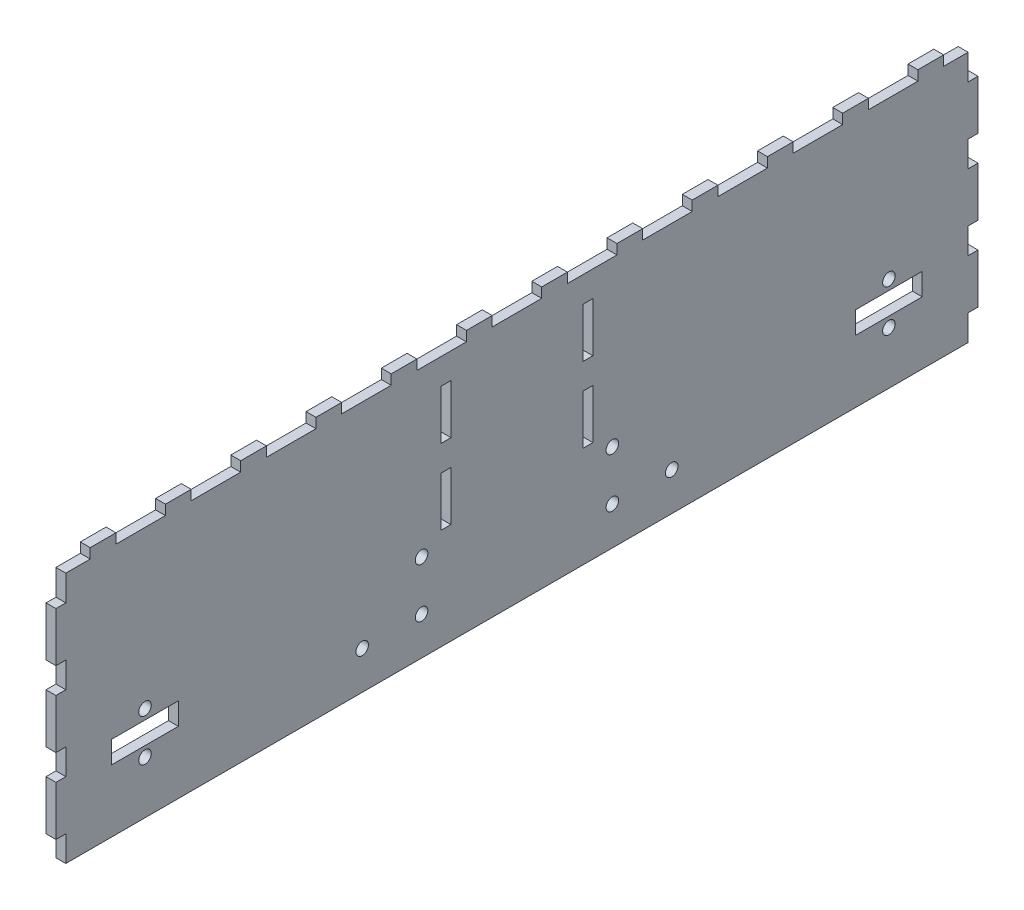
SolidWorks part; units mm, degrees
material "ENPH 253 Hardboard"
ref_plane "Front Plane" through (0, 0, 0) normal (0, 0, 1) x (1, 0, 0)
ref_plane "Top Plane" through (0, 0, 0) normal (0, 1, 0) x (1, 0, 0)
ref_plane "Right Plane" through (0, 0, 0) normal (1, 0, 0) x (0, 0, -1)
sketch "Sketch1" plane through (0, 0, 0) normal (1, 0, 0) x (0, 0, -1)
  line L1 (-139.7, 38.1) -> (139.7, 38.1)
  line L2 (-139.7, 38.1) -> (-139.7, -38.1)
  line L3 (-139.7, -38.1) -> (139.7, -38.1)
  line L4 (139.7, 38.1) -> (139.7, -38.1)
  line L5 (-139.7, 38.1) -> (139.7, -38.1) construction
  line L6 (-139.7, -38.1) -> (139.7, 38.1) construction
  point P0 (0, 0)
  dimension "D1" = 279.4
  dimension "D2" = 76.2
extrude "Boss-Extrude1" add sketch "Sketch1" against normal blind 3 contours L2 L3 L4 L1
sketch "Sketch3" plane through (-3, 0, 0) normal (-1, 0, 0) x (0, 0, 1)
  line L9 (-139.7, 38.1) -> (-136.7, 38.1)
  line L10 (-139.7, 38.1) -> (-139.7, 30.3)
  line L11 (-139.7, 30.3) -> (-136.7, 30.3)
  line L12 (-136.7, 38.1) -> (-136.7, 30.3)
  dimension "D9" = 7.8
  dimension "D10" = 3
extrude "Cut-Extrude1" cut sketch "Sketch3" against normal through all
pattern_linear "LPattern1" count 4 spacing 22.8 along (0, -1, 0) of "Cut-Extrude1"
mirror "Mirror1" about plane through (0, 0, 0) normal (0, 0, 1) of "LPattern1"
sketch "Sketch5" plane through (-3, 0, 0) normal (-1, 0, 0) x (0, 0, 1)
  line L1 (-23, 30.3) -> (-20, 30.3)
  line L2 (-23, 30.3) -> (-23, 15.3)
  line L3 (-23, 15.3) -> (-20, 15.3)
  line L4 (-20, 30.3) -> (-20, 15.3)
  line L5 (136.7, 38.1) -> (-136.7, 38.1) construction
  line L6 (0, -1.65) -> (0, 1.65) construction
  dimension "D1" = 20
  dimension "D2" = 3
  dimension "D3" = 7.8
  dimension "D4" = 15
extrude "Cut-Extrude3" cut sketch "Sketch5" against normal blind 10
sketch "Sketch9" plane through (0, 38.1, 0) normal (0, 1, 0) x (1, 0, 0)
  line L0 (0, -136.7) -> (0, 136.7) construction
  line L1 (0, 129.3) -> (-3, 129.3)
  line L2 (0, 129.3) -> (0, 121.5)
  line L3 (0, 121.5) -> (-3, 121.5)
  line L4 (-3, 129.3) -> (-3, 121.5)
  line L5 (-3, -136.7) -> (-3, 136.7) construction
  line L6 (0, 136.7) -> (-3, 136.7) construction
  point P10 (-1.5, 129.3)
  dimension "D1" = 7.4
  dimension "D2" = 7.8
extrude "Boss-Extrude2" add sketch "Sketch9" along normal blind 3
pattern_linear "LPattern4" count 12 spacing 22.8 along (0, 0, 1) of "Boss-Extrude2"
pattern_linear "LPattern5" count 2 spacing 22.8 along (0, -1, 0) of "Cut-Extrude3"
mirror "Mirror2" about plane through (0, 0, 0) normal (0, 0, 1) of "LPattern5"
hole_wizard "#6 Clearance Hole1" positions "Sketch10" profile "Sketch11" hole size "#6" standard "ANSI Inch" end condition up to next
sketch "Sketch10" plane through (0, 0, 0) normal (1, 0, 0) x (0, 0, -1)
  point P0 (-28.9, -11.55)
  point P3 (-28.9, -26.55)
  point P6 (28.9, -26.55)
  point P9 (28.9, -11.55)
  point P13 (-46.9, -26.55)
  point P16 (46.9, -26.55)
sketch "Sketch11" plane through (0, -11.55, 28.9) normal (0, 1, 0) x (0, 0, -1)
  line L0 (0, 0) -> (0, 3)
  line L1 (0, 3) -> (1.8986, 3)
  line L2 (1.8986, 3) -> (1.8986, 0)
  line L5 (1.8986, 0) -> (0, 0)
  line L11 (0, -6.35) -> (0, 107.95) construction
  dimension "Thru Hole Dia." = 3.7973
  dimension "Thru Hole Depth" = 3
sketch "Sketch12" plane through (0, 0, 0) normal (1, 0, 0) x (0, 0, -1)
  line L0 (0, 38.1) -> (0, -38.1) construction
  line L1 (-122.7, -12.55) -> (-102.7, -12.55) construction
  line L2 (-122.7, -12.55) -> (-122.7, -19.05) construction
  line L3 (-122.7, -19.05) -> (-102.7, -19.05) construction
  line L4 (-102.7, -12.55) -> (-102.7, -19.05) construction
  line L5 (-7.5, 38.1) -> (7.5, 38.1) construction
  line L6 (-136.7, -38.1) -> (136.7, -38.1) construction
  line L8 (-139.7, -15.3) -> (-139.7, -30.3) construction
  line L9 (-122.8, -12.45) -> (-122.8, -19.15)
  line L10 (-122.8, -19.15) -> (-102.6, -19.15)
  line L11 (-102.6, -12.45) -> (-102.6, -19.15)
  line L12 (-122.8, -12.45) -> (-102.6, -12.45)
  line L13 (102.7, -12.55) -> (102.7, -19.05) construction
  line L14 (122.7, -19.05) -> (102.7, -19.05) construction
  line L15 (122.7, -12.55) -> (102.7, -12.55) construction
  line L16 (122.8, -12.45) -> (102.6, -12.45)
  line L17 (102.6, -12.45) -> (102.6, -19.15)
  line L18 (122.8, -19.15) -> (102.6, -19.15)
  line L19 (122.8, -12.45) -> (122.8, -19.15)
  line L20 (122.7, -12.55) -> (122.7, -19.05) construction
  dimension "D1" = 20
  dimension "D2" = 17
  dimension "D3" = 19.05
  dimension "D4" = 6.5
  dimension "D5" = 0.1
extrude "Cut-Extrude4" cut sketch "Sketch12" against normal up to next
hole_wizard "#6 Clearance Hole2" positions "Sketch13" profile "Sketch14" hole size "#6" standard "ANSI Inch" end condition up to next
sketch "Sketch13" plane through (-3, 0, 0) normal (-1, 0, 0) x (0, 0, 1)
  line L0 (-122.8, -12.45) -> (-102.6, -12.45) construction
  line L1 (-102.6, -19.15) -> (-122.8, -19.15) construction
  line L2 (102.6, -12.45) -> (122.8, -12.45) construction
  line L3 (122.8, -19.15) -> (102.6, -19.15) construction
  point P0 (-112.7, -9.45)
  point P2 (-112.7, -22.15)
  point P4 (112.7, -22.15)
  point P6 (112.7, -9.45)
  point P14 (-112.7, -12.45)
  point P17 (112.7, -12.45)
  dimension "D1" = 3
  dimension "D2" = 3
  dimension "D3" = 3
  dimension "D4" = 3
sketch "Sketch14" plane through (-3, -9.45, -112.7) normal (0, 1, 0) x (0, 0, 1)
  line L0 (0, 0) -> (0, 3)
  line L1 (0, 3) -> (1.8986, 3)
  line L2 (1.8986, 3) -> (1.8986, 0)
  line L5 (1.8986, 0) -> (0, 0)
  line L11 (0, -6.35) -> (0, 107.95) construction
  dimension "Thru Hole Dia." = 3.7973
  dimension "Thru Hole Depth" = 3
